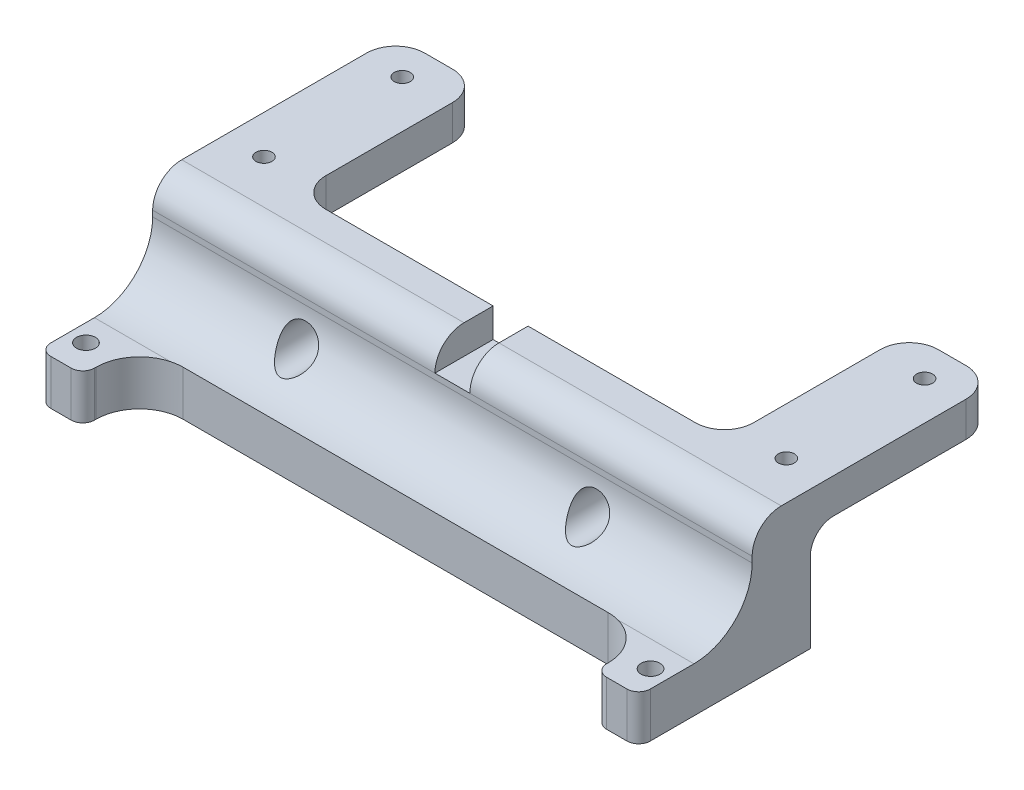
SolidWorks part; units mm, degrees
material "ABS"
ref_plane "Front Plane" through (0, 0, 0) normal (0, 0, 1) x (1, 0, 0)
ref_plane "Top Plane" through (0, 0, 0) normal (0, 1, 0) x (1, 0, 0)
ref_plane "Right Plane" through (0, 0, 0) normal (1, 0, 0) x (0, 0, -1)
sketch "Sketch1" plane through (0, 0, 0) normal (0, 1, 0) x (1, 0, 0)
  line L0 (0, 0) -> (48.5, 0)
  line L1 (53, 0) -> (53, 10)
  line L2 (44, 0) -> (44, 10)
  line L3 (44, 10) -> (53, 10)
  line L4 (53, 10) -> (53, 40)
  line L5 (44, 10) -> (24.25, 10)
  line L6 (24.25, 10) -> (24.25, 20)
  line L7 (24.25, 40) -> (53, 40)
  line L8 (24.25, 20) -> (44, 20)
  line L9 (44, 20) -> (44, 30)
  line L10 (44, 30) -> (24.25, 30)
  line L11 (24.25, 30) -> (24.25, 40)
  line L12 (24.25, 10) -> (0, 10)
  line L13 (24.25, 30) -> (0, 30)
  line L14 (24.25, 20) -> (0, 20)
  line L15 (24.25, 20) -> (24.25, 10)
  line L16 (24.25, 10) -> (0, 10)
  line L17 (0, 20) -> (0, 10)
  line L19 (0, 30) -> (24.25, 30)
  line L20 (0, 30) -> (0, 40)
  line L21 (0, 40) -> (24.25, 40)
  line L22 (24.25, 30) -> (24.25, 40)
  circle A0 centre (48.5, 0) radius 1.5
  circle A1 centre (48.5, 0) radius 4.5
  dimension "D2" = 3
  dimension "D3" = 9
  dimension "D1" = 48.5
  dimension "D4" = 10
  dimension "D5" = 30
  dimension "D6" = 10
  dimension "D7" = 10
extrude "Boss-Extrude1" add sketch "Sketch1" along normal blind 7.75 contours A1 A0 | A1 L1 L3 L2 | L7 L5 L3 L4 | L14 L17 L12 L6 | L21 L20 L13 L11 region at (48.5, 0, -6.6891) region at (48.5, 0, -4.3727) region at (34.125, 0, -10.4155) region at (12.125, 0, -15) region at (12.125, 0, -35)
mirror "Mirror1" about plane through (0, 0, 0) normal (1, 0, 0) of "Boss-Extrude1"
sketch "Sketch5" plane through (0, 7.75, 0) normal (0, 1, 0) x (1, 0, 0)
  line L0 (53, 40) -> (53, 30)
  line L1 (53, 0) -> (53, 40) construction
  line L2 (53, 30) -> (-53, 30)
  line L3 (-53, 0) -> (-53, 40) construction
  line L4 (-53, 30) -> (-53, 40)
  line L5 (-53, 40) -> (53, 40)
  dimension "D1" = 10
extrude "Boss-Extrude3" add sketch "Sketch5" along normal blind 16
sketch "Sketch7" plane through (0, 23.75, 0) normal (0, 1, 0) x (1, 0, 0)
  line L0 (53, 30) -> (36.75, 30)
  line L1 (-53, 30) -> (53, 30) construction
  line L2 (53, 30) -> (53, 71.75)
  line L4 (53, 71.75) -> (36.75, 71.75)
  line L5 (53, 71.75) -> (53, 30)
  line L6 (53, 30) -> (36.75, 30)
  line L7 (36.75, 71.75) -> (36.75, 30)
  line M3 (53, 40) -> (-53, 40)
  dimension "D1" = 16.25
  dimension "D2" = 41.75
extrude "Boss-Extrude4" add sketch "Sketch7" against normal blind 6 contours L4 L7 L2 M3 region at (44.875, 23.75, -55.875)
sketch "Sketch10" plane through (0, 0, 0) normal (0, -1, 0) x (-1, 0, 0)
  line L0 (-53, 40) -> (-36.75, 40)
  line L1 (53, 40) -> (-53, 40) construction
  line L3 (-44.875, 40) -> (-44.875, 42.5)
  line L4 (-44.875, 42.5) -> (-44.875, 66.25)
  circle A0 centre (-44.875, 42.5) radius 1.375
  circle A1 centre (-44.875, 42.5) radius 2.75
  circle A2 centre (-44.875, 66.25) radius 1.375
  circle A3 centre (-44.875, 66.25) radius 2.75
  dimension "D3" = 2.75
  dimension "D4" = 5.5
  dimension "D6" = 2.75
  dimension "D7" = 5.5
  dimension "D1" = 16.25
  dimension "D2" = 2.5
  dimension "D5" = 23.75
extrude "Cut-Extrude2" cut sketch "Sketch10" against normal through all contours A0 | A2
extrude "Cut-Extrude3" cut sketch "Sketch10<3>" against normal up to surface (17.75 mm away) contours L0 A1 region at (44.875, 0, -39.8996) up to face at (44.875, 17.75, -41.125)
sketch "Sketch10<3>" plane through (0, 0, 0) normal (0, -1, 0) x (-1, 0, 0) same geometry as "Sketch10"
mirror "Mirror2" about plane through (0, 0, 0) normal (1, 0, 0) of "Cut-Extrude3", "Cut-Extrude2", "Boss-Extrude4"
sketch "Sketch11" plane through (0, 23.75, 0) normal (0, 1, 0) x (1, 0, 0)
  line L0 (0, 40) -> (0, 30)
  line L1 (36.75, 40) -> (-36.75, 40) construction
  line L2 (-53, 30) -> (53, 30) construction
  line L3 (0, 30) -> (-3, 30)
  line L4 (0, 40) -> (3, 40)
  line L6 (3, 40) -> (-3, 40)
  line L7 (3, 40) -> (3, 30)
  line L8 (3, 30) -> (-3, 30)
  line L9 (-3, 40) -> (-3, 30)
  line M9 (36.75, 40) -> (-36.75, 40)
  line M13 (-53, 30) -> (53, 30)
  dimension "D1" = 3
extrude "Cut-Extrude4" cut sketch "Sketch11" against normal blind 5 contours L7 L0 M9 M13 | L9 L0 M9 M13 region at (1.5, 23.75, -35) region at (-1.5, 23.75, -35)
sketch "Sketch12" plane through (0, 7.75, 0) normal (0, 1, 0) x (1, 0, 0)
  line L0 (0, 20) -> (0, 10)
  line L1 (-44, 20) -> (44, 20) construction
  line L2 (44, 10) -> (-44, 10) construction
  line L3 (0, 15) -> (25, 15)
  circle A0 centre (25, 15) radius 1.375
  dimension "D2" = 2.75
  dimension "D1" = 25
extrude "Cut-Extrude5" cut sketch "Sketch12" against normal through all contours A0
mirror "Mirror10" about plane through (0, 0, 0) normal (1, 0, 0) of "Cut-Extrude5"
ref_plane "Plane1" through (0, 0, -55.25) normal (0, 0, -1) x (-1, 0, 0)
sketch "Sketch13" plane through (0, 7.75, 0) normal (0, 1, 0) x (1, 0, 0)
  line L0 (-48.5, 0) -> (-48.5, 15.54)
  circle A0 centre (-48.5, 15.54) radius 1.625
  dimension "D2" = 3.25
  dimension "D1" = 15.54
extrude "Cut-Extrude6" cut sketch "Sketch13" against normal through all contours A0
mirror "Mirror11" about plane through (0, 0, 0) normal (1, 0, 0) of "Cut-Extrude6"
sketch "Sketch14" plane through (0, 7.75, 0) normal (0, 1, 0) x (1, 0, 0)
  line L1 (-44, 20) -> (44, 20)
  line L2 (-44, 20) -> (-44, 10)
  line L3 (-44, 10) -> (44, 10)
  line L4 (44, 20) -> (44, 10)
extrude "Cut-Extrude7" cut sketch "Sketch14" against normal through all
ref_plane "Plane2" through (0, 0, -10.5) normal (0, 0, 1) x (1, 0, 0)
sketch "Sketch15" plane through (0, 0, -10.5) normal (0, 0, 1) x (1, 0, 0)
  circle A0 centre (0, 0) radius 80.5336
extrude "Cut-Extrude8" cut sketch "Sketch15" along normal through all
sketch "Sketch16" plane through (53, 0, 0) normal (1, 0, 0) x (0, 0, -1)
  circle A0 centre (0, 0) radius 101.5257
extrude "Cut-Extrude9" cut sketch "Sketch16" against normal blind 1.5
mirror "Mirror12" about plane through (0, 0, 0) normal (1, 0, 0) of "Cut-Extrude9"
sketch "Sketch17" plane through (-44, 0, 0) normal (1, 0, 0) x (0, 0, -1)
  line L0 (30, 7.75) -> (20.25, 7.75)
  line L1 (10.5, 7.75) -> (30, 7.75) construction
  line L2 (20.25, 7.75) -> (20.25, 0)
  line L3 (10.5, 0) -> (30, 0) construction
  line L4 (20.25, 0) -> (30, 0)
  line L5 (30, 0) -> (30, 7.75)
extrude "Boss-Extrude5" add sketch "Sketch17" along normal up to next
fillet "Fillet1" radius 2 1 edges at (51.5, 3.875, -10.5) type face fillet first side face at (51.5, 12.3125, -38.0625) second side face at (47.75, 3.875, -10.5)
fillet "Fillet2" radius 2 1 edges at (44, 3.875, -10.5) type face fillet first side face at (46.75, 3.875, -10.5) second side face at (44, 3.875, -15.375)
fillet "Fillet3" radius 2 1 edges at (-44, 3.875, -10.5) type face fillet first side face at (-44, 3.875, -15.375) second side face at (-47.75, 3.875, -10.5)
fillet "Fillet4" radius 2 1 edges at (-51.5, 3.875, -10.5) type face fillet first side face at (-51.5, 12.3125, -38.0625) second side face at (-48.75, 3.875, -10.5)
fillet "Fillet5" radius 7.5 1 edges at (-44, 3.875, -20.25) type face fillet first side face at (0, 3.875, -20.25) second side face at (-44, 3.875, -16.375)
fillet "Fillet6" radius 7.5 1 edges at (44, 3.875, -20.25) type face fillet first side face at (44, 3.875, -16.375) second side face at (3.75, 3.875, -20.25)
fillet "Fillet8" radius 10 1 edges at (0, 7.75, -30) type face fillet first side face at (0, 18.5, -30) second side face at (48.5, 7.75, -13.915)
fillet "Fillet9" radius 5 1 edges at (51.5, 20.75, -71.75) type face fillet first side face at (51.5, 12.6865, -36.7301) second side face at (44.125, 20.75, -71.75)
fillet "Fillet10" radius 5 1 edges at (36.75, 20.75, -71.75) type face fillet first side face at (36.75, 20.75, -55.875) second side face at (41.625, 20.75, -71.75)
fillet "Fillet11" radius 5 1 edges at (-51.5, 20.75, -71.75) type face fillet first side face at (-51.5, 12.6865, -36.7301) second side face at (-44.125, 20.75, -71.75)
fillet "Fillet12" radius 5 1 edges at (-36.75, 20.75, -71.75) type face fillet first side face at (-41.625, 20.75, -71.75) second side face at (-36.75, 20.75, -55.875)
fillet "Fillet13" radius 5 1 edges at (40.2397, 17.75, -40) type face fillet first side face at (0, 16.9583, -40) second side face at (44.875, 17.75, -64.875)
fillet "Fillet14" radius 5 1 edges at (-40.2397, 17.75, -40) type face fillet first side face at (0, 16.125, -40) second side face at (-44.875, 17.75, -64.875)
fillet "Fillet15" radius 4 1 edges at (-48.7603, 17.75, -40) type face fillet first side face at (-48.7603, 8.875, -40) second side face at (-44.875, 17.75, -64.875)
fillet "Fillet16" radius 4 1 edges at (48.7603, 17.75, -40) type face fillet first side face at (48.7603, 8.875, -40) second side face at (44.875, 17.75, -64.875)
fillet "Fillet17" radius 5 1 edges at (-27.25, 23.75, -30) type face fillet first side face at (-44.875, 23.75, -67.625) second side face at (0, 21, -30)
fillet "Fillet18" radius 5 1 edges at (27.25, 23.75, -30) type face fillet first side face at (44.875, 23.75, -67.625) second side face at (0.4286, 19.8929, -30)
fillet "Fillet19" radius 5 1 edges at (36.75, 18.25, -40) type face fillet first side face at (0, 15.2917, -40) second side face at (36.75, 19.3571, -51.4929)
fillet "Fillet20" radius 5 1 edges at (-36.75, 18.25, -40) type face fillet first side face at (-36.75, 19.3571, -51.4929) second side face at (-0.8333, 15.2917, -40)
sketch "Sketch19" plane through (0, 0, 0) normal (0, 0, 1) x (1, 0, 0)
  line L0 (0, 0) -> (0, 12.5)
  line L1 (0, 12.5) -> (-25, 12.5)
  circle A0 centre (-25, 12.5) radius 1.625
  circle A1 centre (-25, 12.5) radius 3.125
  dimension "D2" = 3.25
  dimension "D3" = 6.25
  dimension "D1" = 12.5
extrude "Cut-Extrude11" cut sketch "Sketch19" against normal through all contours A0 region at (-26.579, 12.5, 0)
extrude "Cut-Extrude12" cut sketch "Sketch19<3>" against normal blind 35 contours A1 A0 region at (-28.0366, 12.5, 0)
sketch "Sketch19<3>" plane through (0, 0, 0) normal (0, 0, 1) x (1, 0, 0) same geometry as "Sketch19"
mirror "Mirror15" about plane through (0, 0, 0) normal (1, 0, 0) of "Cut-Extrude12", "Cut-Extrude11"
